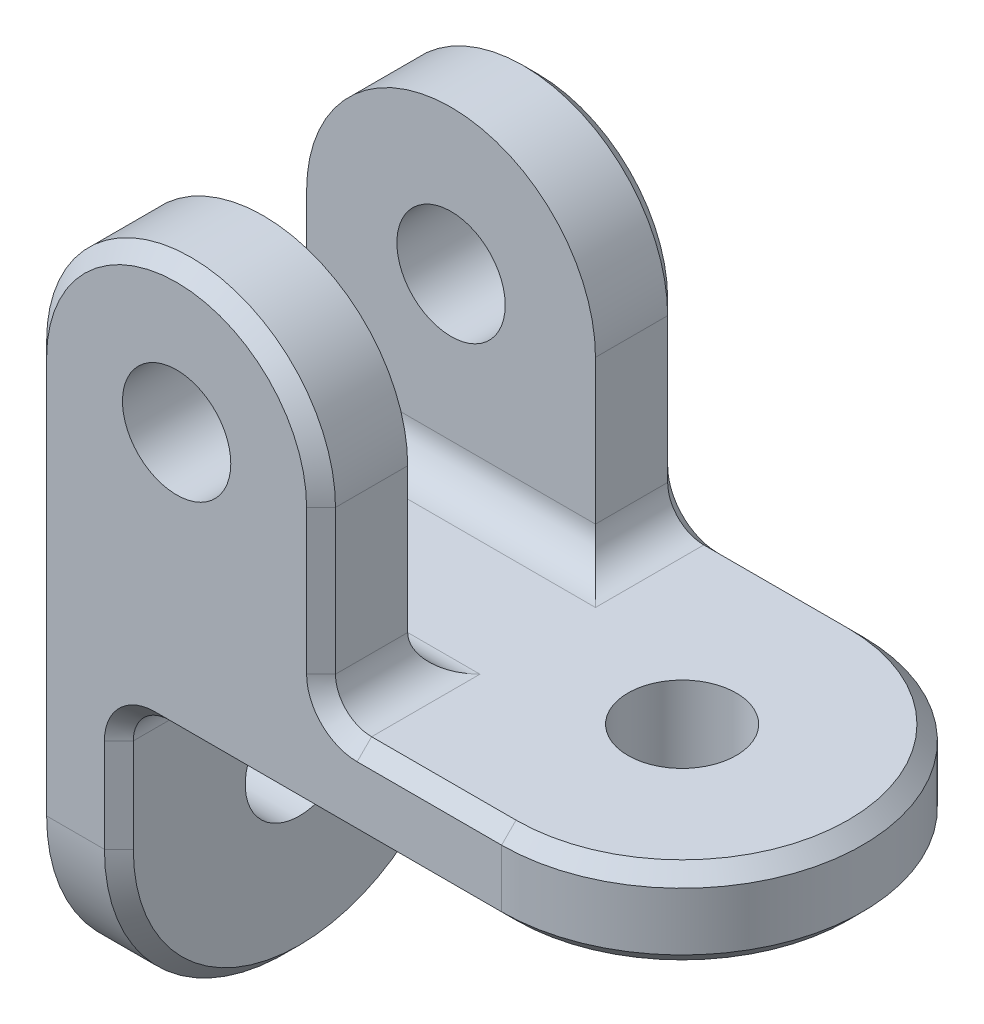
SolidWorks part; units mm, degrees
ref_plane "Front Plane" through (0, 0, 0) normal (0, 0, 1) x (1, 0, 0)
ref_plane "Top Plane" through (0, 0, 0) normal (0, 1, 0) x (1, 0, 0)
ref_plane "Right Plane" through (0, 0, 0) normal (1, 0, 0) x (0, 0, -1)
sketch "Sketch1" plane through (0, 0, 0) normal (0, 1, 0) x (1, 0, 0)
  line L1 (-45, 25) -> (20, 25)
  line L2 (-45, 25) -> (-45, -25)
  line L3 (-45, -25) -> (20, -25)
  line L5 (-45, 25) -> (35.4202, -19.6779) construction
  line L6 (-45, -25) -> (35.4202, 19.6779) construction
  arc A1 (20, -25) -> (20, 25) centre (20, 0) ccw
  point P0 (0, 0)
  point P4 (0, 0)
  point P7 (0, 0)
  dimension "D3" = 25
  dimension "D1" = 65
  dimension "D2" = 50
extrude "Boss-Extrude1" add sketch "Sketch1" along normal mid plane 12
sketch "Sketch2" plane through (0, 0, 0) normal (0, 0, 1) x (1, 0, 0)
  line L1 (-45, 6) -> (-5, 6)
  line L2 (-45, 6) -> (-45, 31)
  line L4 (-5, 6) -> (-5, 31)
  arc A0 (-5, 31) -> (-45, 31) centre (-25, 31) ccw
  dimension "D4" = 40
  dimension "D5" = 20
extrude "Boss-Extrude2" add sketch "Sketch2" along normal mid plane 12 from offset 19
extrude "Boss-Extrude3" add sketch "Sketch2<2>" along normal mid plane 12 from offset 19 offset against normal yes
sketch "Sketch2<2>" plane through (0, 0, 0) normal (0, 0, 1) x (1, 0, 0) same geometry as "Sketch2"
sketch "Sketch3" plane through (0, 0, 0) normal (1, 0, 0) x (0, 0, -1)
  line L1 (-25, -6) -> (25, -6)
  line L2 (-25, -6) -> (-25, -24)
  line L4 (25, -6) -> (25, -24)
  arc A0 (-25, -24) -> (25, -24) centre (0, -24) ccw
  dimension "D3" = 50
  dimension "D5" = 25
extrude "Boss-Extrude4" add sketch "Sketch3" along normal mid plane 12 from offset 39 offset against normal yes
sketch "Sketch4" plane through (0, 0, 0) normal (1, 0, 0) x (0, 0, -1)
  circle A0 centre (0, -24) radius 7.5
  arc A2 (-25, -24) -> (25, -24) centre (0, -24) ccw construction
  point P2 (0, 0)
  point P6 (0, 0)
  dimension "D1" = 15
  dimension "D2" = 0
  dimension "D3" = 25
sketch "Sketch6" plane through (0, 0, 0) normal (0, 1, 0) x (1, 0, 0)
  circle A0 centre (20, 0) radius 7.5
  arc A1 (20, -25) -> (20, 25) centre (20, 0) ccw construction
  dimension "D1" = 15
  dimension "D2" = 0
  dimension "D3" = 25
sketch "Sketch7" plane through (0, 0, 0) normal (0, 0, 1) x (1, 0, 0)
  circle A0 centre (-25, 31) radius 7.5
  arc A1 (-5, 31) -> (-45, 31) centre (-25, 31) ccw construction
  dimension "D1" = 15
  dimension "D2" = 0
  dimension "D3" = 0
extrude "Cut-Extrude1" cut sketch "Sketch7" against normal mid plane 50
extrude "Cut-Extrude2" cut sketch "Sketch4" against normal through all contours A0
extrude "Cut-Extrude3" cut sketch "Sketch6" against normal mid plane 20 contours A0
fillet "Fillet1" radius 5 5 edges at (-33, -6, 0) (-25, 6, -13) (-5, 6, -19) (-25, 6, 13) (-5, 6, 19)
chamfer "Chamfer1" distance 2 angle 45 20 edges at (45, -6, 0) (-4, -6, 25) (-4, -6, -25) (-31.5355, -7.4645, -25) (-31.5355, -7.4645, 25) (-33, -17.5, -25) (-33, -17.5, 25) (-33, -49, 0) (-45, -49, 0) (-45, 3.5, 25) (-45, 3.5, -25) (-25, 51, -25) (-5, 21, -25) (-3.5355, 7.4645, -25) (10, 6, -25) (45, 6, 0) (10, 6, 25) (-3.5355, 7.4645, 25) (-5, 21, 25) (-25, 51, 25)
